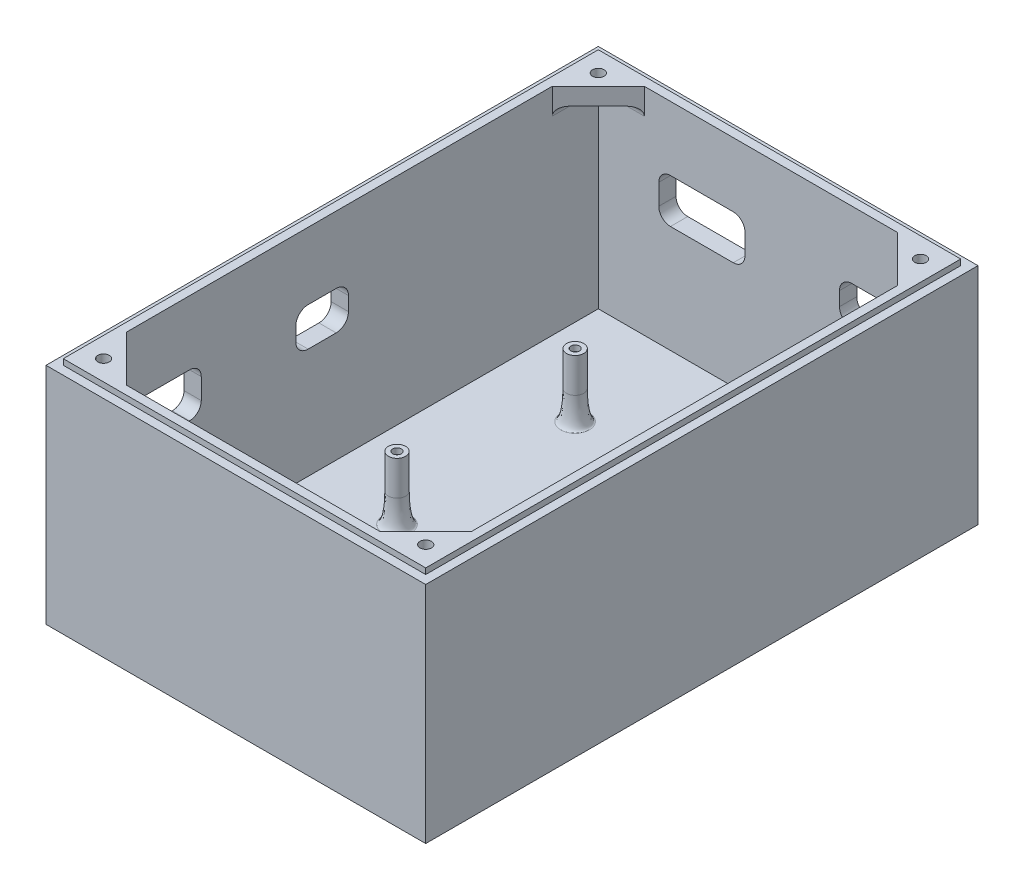
SolidWorks part; units mm, degrees
ref_plane "Front Plane" through (0, 0, 0) normal (0, 0, 1) x (1, 0, 0)
ref_plane "Top Plane" through (0, 0, 0) normal (0, 1, 0) x (1, 0, 0)
ref_plane "Right Plane" through (0, 0, 0) normal (1, 0, 0) x (0, 0, -1)
sketch "Sketch1" plane through (0, 0, 0) normal (0, 1, 0) x (1, 0, 0)
  line L0 (-60, 0) -> (60, 0) construction
  line L1 (-60, 90) -> (60, 90)
  line L2 (-60, 90) -> (-60, -90)
  line L3 (-60, -90) -> (60, -90)
  line L4 (60, 90) -> (60, -90)
  line L6 (-66, 96) -> (66, 96)
  line L7 (-66, 96) -> (-66, -96)
  line L8 (-66, -96) -> (66, -96)
  line L9 (66, 96) -> (66, -96)
  line L10 (-66, 96) -> (66, -96) construction
  line L11 (-66, -96) -> (66, 96) construction
  point P4 (0, 0)
  dimension "D1" = 120
  dimension "D2" = 180
  dimension "D3" = 6
  dimension "D4" = 6
extrude "Boss-Extrude1" add sketch "Sketch1" along normal blind 80
sketch "Sketch2" plane through (0, 0, 0) normal (0, -1, 0) x (-1, 0, 0)
  line L1 (66, 96) -> (-66, 96)
  line L2 (66, 96) -> (66, -96)
  line L3 (66, -96) -> (-66, -96)
  line L4 (-66, 96) -> (-66, -96)
extrude "Boss-Extrude2" add sketch "Sketch2" against normal blind 5
sketch "Sketch3" plane through (0, 0, -96) normal (0, 0, -1) x (-1, 0, 0)
  line L0 (0, 80) -> (0, 0) construction
  line L5 (-66, 80) -> (66, 80) construction
  line L6 (0, 80) -> (-66, 80)
  line L11 (-33, 80) -> (-33, 0) construction
  line L12 (-66, 0) -> (66, 0) construction
  line L17 (13.085, 57.67) -> (34.915, 57.67)
  line L18 (9.025, 53.61) -> (9.025, 46.39)
  line L19 (-37.875, 56.69) -> (-28.125, 56.69)
  line L20 (-42.145, 52.42) -> (-42.145, 47.58)
  line L21 (-37.875, 43.31) -> (-28.125, 43.31)
  line L22 (-23.855, 52.42) -> (-23.855, 47.58)
  line L23 (-42.145, 56.69) -> (-23.855, 43.31) construction
  line L24 (-42.145, 43.31) -> (-23.855, 56.69) construction
  line L25 (13.085, 42.33) -> (34.915, 42.33)
  line L26 (38.975, 53.61) -> (38.975, 46.39)
  line L27 (9.025, 57.67) -> (38.975, 42.33) construction
  line L28 (9.025, 42.33) -> (38.975, 57.67) construction
  line L29 (66, 80) -> (66, 0) construction
  line L30 (24, 80) -> (24, 0) construction
  arc A8 (-42.145, 47.58) -> (-37.875, 43.31) centre (-37.875, 47.58) ccw
  arc A9 (-28.125, 43.31) -> (-23.855, 47.58) centre (-28.125, 47.58) ccw
  arc A10 (-28.125, 56.69) -> (-23.855, 52.42) centre (-28.125, 52.42) cw
  arc A11 (-37.875, 56.69) -> (-42.145, 52.42) centre (-37.875, 52.42) ccw
  arc A12 (9.025, 46.39) -> (13.085, 42.33) centre (13.085, 46.39) ccw
  arc A13 (34.915, 42.33) -> (38.975, 46.39) centre (34.915, 46.39) ccw
  arc A14 (34.915, 57.67) -> (38.975, 53.61) centre (34.915, 53.61) cw
  arc A15 (13.085, 57.67) -> (9.025, 53.61) centre (13.085, 53.61) ccw
  point P3 (-33, 80)
  point P10 (24, 50)
  point P16 (-33, 50)
  point P30 (0, 0)
  point P34 (33, 80)
  dimension "D7" = 30
  dimension "D10" = 4.27
  dimension "D6" = 4.06
  dimension "D2" = 30
  dimension "D3" = 15.34
  dimension "D4" = 29.95
  dimension "D5" = 42
  dimension "D9" = 18.29
  dimension "D11" = 13.38
extrude "Cut-Extrude1" cut sketch "Sketch3" against normal up to surface (6 mm away) contours L19 A11 L20 A8 L21 A9 L22 A10 | L17 A15 L18 A12 L25 A13 L26 A14 region at (-24, 50, -96) region at (33, 50, -96) up to face at (0, 42.5, -90)
sketch "Sketch4" plane through (-66, 0, 0) normal (-1, 0, 0) x (0, 0, 1)
  line L0 (-96, 80) -> (96, 80) construction
  line L4 (96, 80) -> (96, 0) construction
  line L5 (6, 80) -> (6, 0) construction
  line L11 (52.085, 57.67) -> (73.915, 57.67)
  line L16 (48.025, 53.61) -> (48.025, 46.39)
  line L21 (1.125, 56.69) -> (10.875, 56.69)
  line L22 (-3.145, 52.42) -> (-3.145, 47.58)
  line L25 (1.125, 43.31) -> (10.875, 43.31)
  line L26 (15.145, 52.42) -> (15.145, 47.58)
  line L27 (-3.145, 56.69) -> (15.145, 43.31) construction
  line L28 (-3.145, 43.31) -> (15.145, 56.69) construction
  line L29 (52.085, 42.33) -> (73.915, 42.33)
  line L30 (77.975, 53.61) -> (77.975, 46.39)
  line L31 (48.025, 57.67) -> (77.975, 42.33) construction
  line L32 (48.025, 42.33) -> (77.975, 57.67) construction
  line L34 (63, 80) -> (63, 0) construction
  line L37 (-96, 0) -> (96, 0) construction
  arc A8 (-3.145, 47.58) -> (1.125, 43.31) centre (1.125, 47.58) ccw
  arc A9 (10.875, 43.31) -> (15.145, 47.58) centre (10.875, 47.58) ccw
  arc A10 (10.875, 56.69) -> (15.145, 52.42) centre (10.875, 52.42) cw
  arc A11 (1.125, 56.69) -> (-3.145, 52.42) centre (1.125, 52.42) ccw
  arc A12 (48.025, 46.39) -> (52.085, 42.33) centre (52.085, 46.39) ccw
  arc A13 (73.915, 42.33) -> (77.975, 46.39) centre (73.915, 46.39) ccw
  arc A14 (73.915, 57.67) -> (77.975, 53.61) centre (73.915, 53.61) cw
  arc A15 (52.085, 57.67) -> (48.025, 53.61) centre (52.085, 53.61) ccw
  point P3 (-3.8197, 80)
  point P6 (63, 50)
  point P11 (6, 50)
  point P27 (63.9138, 80)
  point P44 (94.1977, 77.8718)
  point P45 (96, 80)
  point P50 (63.5979, 0)
  point P53 (31.8276, 0)
  point P54 (-3.8197, 0)
  dimension "D5" = 29.95
  dimension "D6" = 4.06
  dimension "D2" = 4.27
  dimension "D1" = 18.29
  dimension "D3" = 13.38
  dimension "D4" = 15.34
  dimension "D7" = 30
  dimension "D8" = 30
  dimension "D9" = 57
  dimension "D10" = 33
extrude "Cut-Extrude2" cut sketch "Sketch4" against normal up to surface (6 mm away) up to face at (-60, 42.5, 0)
sketch "Sketch5" plane through (0, 5, 0) normal (0, 1, 0) x (1, 0, 0)
  line L1 (-30.089, 52.032) -> (42.047, 52.032)
  line L2 (-30.089, 52.032) -> (-30.089, -71.793)
  line L3 (-30.089, -71.793) -> (42.047, -71.793)
  line L4 (42.047, 52.032) -> (42.047, -71.793)
  circle A0 centre (-30.089, 52.032) radius 3
  circle A1 centre (42.047, 52.032) radius 3
  circle A2 centre (-30.089, -71.793) radius 3
  circle A3 centre (42.047, -71.793) radius 3
  circle A5 centre (-30.089, -9.8805) radius 3
  circle A6 centre (42.047, -9.8805) radius 3
  dimension "D1" = 6
extrude "Boss-Extrude3" add sketch "Sketch5" along normal blind 22 contours L4 A1 L1 | L1 A1 L4 | L3 A3 L4 | L4 A3 L3 | L1 A0 L2 | L2 A0 L1 | L3 A2 L2 | L2 A2 L3 | L2 A5 | L2 A5 | L4 A6 | L4 A6 region at (-30.5134, 5, -52.4564) region at (-28.8158, 5, -50.7588) region at (42.4714, 5, -52.4564) region at (40.7738, 5, -50.7588) region at (-28.8158, 5, 9.8805) region at (-31.3622, 5, 9.8805) region at (43.3202, 5, 9.8805) region at (40.7738, 5, 9.8805) region at (-28.8158, 5, 70.5198) region at (-30.5134, 5, 72.2174) region at (42.4714, 5, 72.2174) region at (40.7738, 5, 70.5198)
fillet "Fillet2" radius 2 6 edges at (-30.089, 5, 74.793) (-30.089, 5, 12.8805) (-30.089, 5, -49.032) (42.047, 5, 74.793) (42.047, 5, 12.8805) (42.047, 5, -49.032) second distance 10 first distance on face at (42.047, 5, 12.8805)
sketch "Sketch7" plane through (0, 80, 0) normal (0, 1, 0) x (1, 0, 0)
  line L0 (-60, 0) -> (60, 0) construction
  line L1 (-60, 90) -> (-52, 90)
  line L2 (-60, 90) -> (-60, 82)
  line L3 (-60, 82) -> (-52, 82)
  line L4 (-52, 90) -> (-52, 82)
  line L5 (-60, 90) -> (-60, -90) construction
  line L6 (60, -90) -> (60, 90) construction
  line L7 (-52, -90) -> (-52, -82)
  line L8 (-60, -82) -> (-52, -82)
  line L9 (-60, -90) -> (-60, -82)
  line L10 (-60, -90) -> (-52, -90)
  line L11 (0, 90) -> (0, -90) construction
  line L16 (60, 90) -> (-60, 90) construction
  line L17 (-60, -90) -> (60, -90) construction
  line L22 (60, -90) -> (52, -90)
  line L23 (60, -90) -> (60, -82)
  line L24 (60, -82) -> (52, -82)
  line L25 (52, -90) -> (52, -82)
  line L26 (52, 90) -> (52, 82)
  line L27 (60, 82) -> (52, 82)
  line L28 (60, 90) -> (60, 82)
  line L29 (60, 90) -> (52, 90)
  line L30 (-56, 90) -> (-56, 82) construction
  line L31 (-60, 86) -> (-52, 86) construction
  line L32 (-60, -82) -> (-52, -90) construction
  line L33 (52, -82) -> (60, -90) construction
  line L34 (-44, 90) -> (-60, 74)
  line L35 (60, 90) -> (-60, 90) construction
  line L36 (44, 90) -> (60, 74)
  line L37 (44, -90) -> (60, -74)
  line L38 (-44, -90) -> (-60, -74)
  circle A0 centre (-56, 86) radius 2
  circle A1 centre (56, 86) radius 2
  circle A3 centre (56, -86) radius 2
  circle A5 centre (-56, -86) radius 2
  circle A6 centre (-56, 0) radius 2 [skipped]
  circle A7 centre (56, 0) radius 2 [skipped]
  point P17 (-52, 82)
  point P18 (0, 0)
  point P43 (56, -86)
  point P45 (-56, -86)
  line M13 (60, -90) -> (-60, -90)
  line M14 (-60, -90) -> (-60, 90)
  line M15 (-60, 90) -> (60, 90)
  line M16 (60, 90) -> (60, -90)
  dimension "D5" = 4
  dimension "D1" = 8
  dimension "D2" = 8
  dimension "D6" = 2
  dimension "D7" = 3
extrude "Boss-Extrude4" add sketch "Sketch7" against normal blind 6 contours L4 L3 A0 M15 M14 | L34 L3 M14 | L34 L4 M15 | L36 L26 M15 | L27 L26 A1 M16 M15 | L27 L36 M16 | L37 L25 M13 | L25 L24 A3 M13 M16 | L37 L24 M16 | L8 L7 A5 M14 M13 | L8 L38 M14 | L38 L7 M13 region at (-56, 80, -89.8869) region at (-49.3333, 80, -87.3333) region at (-57.3333, 80, -79.3333) region at (49.3333, 80, -87.3333) region at (-57.3333, 80, 79.3333) region at (52.1131, 80, -86) region at (57.3333, 80, -79.3333) region at (-49.3333, 80, 87.3333) region at (-52.1131, 80, 86) region at (57.3333, 80, 79.3333) region at (49.3333, 80, 87.3333) region at (56, 80, 82.1131)
sketch "Sketch9" plane through (0, 80, 0) normal (0, 1, 0) x (1, 0, 0)
  line L5 (-66, 96) -> (66, 96)
  line L6 (-66, 96) -> (-66, -96)
  line L7 (-66, -96) -> (66, -96)
  line L8 (-63, -93) -> (63, -93)
  line L9 (63, -93) -> (63, 93)
  line L10 (-63, 93) -> (-63, -93)
  line L11 (63, 93) -> (-63, 93)
  line L12 (-63, -93) -> (63, -93)
  line L13 (63, -93) -> (63, 93)
  line L14 (-63, 93) -> (-63, -93)
  line L15 (63, 93) -> (-63, 93)
  line L16 (66, 96) -> (66, -96)
  dimension "D1" = 3
extrude "Cut-Extrude3" cut sketch "Sketch9" against normal blind 2
fillet "Fillet5" radius 3 8 edges at (52, 74, 90) (60, 74, 82) (60, 74, -82) (52, 74, -90) (-60, 74, 82) (-52, 74, 90) (-52, 74, -90) (-60, 74, -82)
sketch "Sketch10" plane through (0, 27, 0) normal (0, 1, 0) x (1, 0, 0)
  circle A0 centre (-30.089, 52.032) radius 1.5
  circle A1 centre (42.047, 52.032) radius 1.5
  circle A2 centre (42.047, -9.8805) radius 1.5
  circle A3 centre (42.047, -71.793) radius 1.5
  circle A4 centre (-30.089, -71.793) radius 1.5
  circle A5 centre (-30.089, -9.8805) radius 1.5
  dimension "D1" = 3
extrude "Cut-Extrude4" cut sketch "Sketch10" against normal blind 2
equation "\"length\"= 120"
equation "\"D1@Sketch1\"=\"length\""
equation "\"width\"= 180"
equation "\"D2@Sketch1\"=\"width\""
equation "\"wall_thickness\"= 6"
equation "\"D3@Sketch1\"=\"wall_thickness\""
equation "\"D4@Sketch1\"=\"wall_thickness\""
equation "\"hieght\"= 80"
equation "\"D1@Boss-Extrude1\"=\"hieght\""
equation "\"base_thickness\"= 5"
equation "\"D1@Boss-Extrude2\"=\"base_thickness\""
